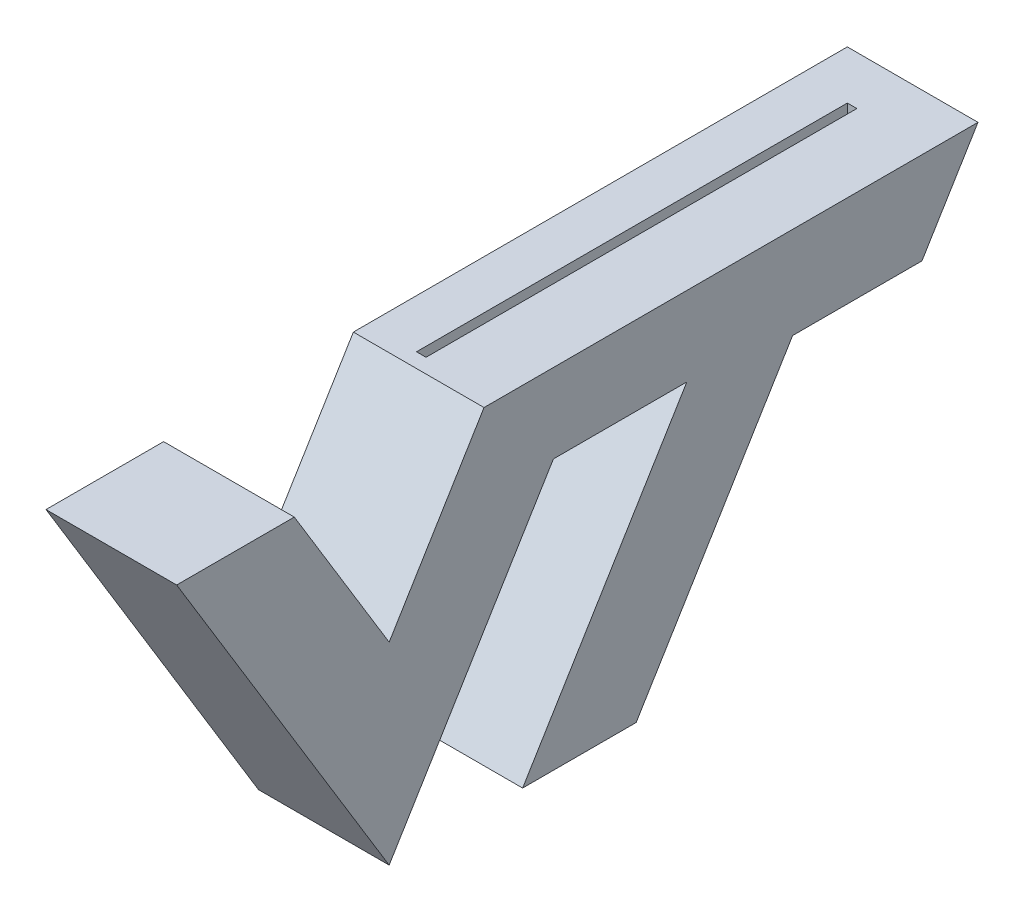
SolidWorks part; units mm, degrees
ref_plane "Front Plane" through (0, 0, 0) normal (0, 0, 1) x (1, 0, 0)
ref_plane "Top Plane" through (0, 0, 0) normal (0, 1, 0) x (1, 0, 0)
ref_plane "Right Plane" through (0, 0, 0) normal (1, 0, 0) x (0, 0, -1)
sketch "Sketch1" plane through (0, 0, 0) normal (1, 0, 0) x (0, 0, -1)
  line L0 (-48.1539, 15.6688) -> (-48.1539, -8.5378) construction
  line L1 (-80.0734, 20.9298) -> (-48.1539, -31.4755)
  line L2 (-16.2343, 20.9298) -> (-48.1539, -31.4755)
  line L3 (-80.0734, 20.9298) -> (-89.454, 36.3307)
  line L4 (-66.594, 36.3307) -> (-48.1539, 6.0559)
  line L5 (-29.7138, 36.3307) -> (-48.1539, 6.0559)
  line L6 (-16.2343, 20.9298) -> (9.7042, 20.9298)
  line L7 (9.7042, 20.9298) -> (-22.2153, -31.4755)
  line L8 (-22.2153, -31.4755) -> (-0.1479, -31.4755)
  line L9 (-0.1479, -31.4755) -> (30.2617, 18.4507)
  line L10 (30.2617, 18.4507) -> (55.4077, 18.4507)
  line L11 (55.4077, 18.4507) -> (66.2982, 36.3307)
  line L12 (66.2982, 36.3307) -> (-29.7138, 36.3307)
  line L13 (-66.594, 36.3307) -> (-89.454, 36.3307)
  line L14 (-73.6825, 21.4236) -> (-48.1539, -20.4892)
  line L15 (-20.955, 24.1657) -> (-48.1539, -20.4892)
  line L16 (-20.955, 24.1657) -> (17.5743, 24.1657)
  line L17 (17.5743, 24.1657) -> (-12.8352, -25.7605)
  line L18 (-12.8352, -25.7605) -> (-3.3586, -25.7605)
  line L19 (-3.3586, -25.7605) -> (27.051, 24.1657)
  line L20 (27.051, 24.1657) -> (52.197, 24.1657)
  line L21 (52.197, 24.1657) -> (56.1256, 30.6157)
  line L22 (56.1256, 30.6157) -> (-26.503, 30.6157)
  line L23 (-26.503, 30.6157) -> (-48.1539, -4.9304)
  line L24 (-69.8047, 30.6157) -> (-48.1539, -4.9304)
  line L25 (-69.8047, 30.6157) -> (-79.2813, 30.6157)
  line L26 (-73.6825, 21.4236) -> (-79.2813, 30.6157)
  point P1 (0, 0)
  point P2 (0, 0)
  point P4 (9.7042, 20.9298)
  dimension "D1" = 31.345
  dimension "D2" = 31.345
  dimension "D3" = 90
extrude "Boss-Extrude3" add sketch "Sketch1" along normal blind 25.4 contours L1 L2 L6 L7 L8 L9 L10 L11 L12 L5 L4 L13 L3
extrude "Cut-Extrude2" cut sketch "Sketch1<7>" along normal blind 20.32 from offset 2.54 contours L14 L15 L16 L17 L18 L19 L20 L21 L22 L23 L24 L25 L26
sketch "Sketch1<7>" plane through (0, 0, 0) normal (1, 0, 0) x (0, 0, -1) same geometry as "Sketch1"
sketch "Sketch4" plane through (0, 36.3307, 0) normal (0, 1, 0) x (1, 0, 0)
  line L1 (4.9967, 59.1862) -> (16.0423, 59.1862)
  line L2 (4.9967, 59.1862) -> (4.9967, -29.7138)
  line L3 (4.9967, -29.7138) -> (16.0423, -29.7138)
  line L4 (16.0423, 59.1862) -> (16.0423, -29.7138)
  line L5 (25.4, -29.7138) -> (0, -29.7138) construction
  line L6 (9.4419, 56.7338) -> (10.9623, 56.7338)
  line L7 (9.4419, 56.7338) -> (9.4419, -26.2393)
  line L8 (9.4419, -26.2393) -> (10.9623, -26.2393)
  line L9 (10.9623, 56.7338) -> (10.9623, -26.2393)
  dimension "D1" = 88.9
  dimension "D2" = 0
  dimension "D3" = 5.08
extrude "Boss-Extrude4" add sketch "Sketch4" against normal blind 11.684
sketch "Sketch6" plane through (0, 36.3307, 0) normal (0, 1, 0) x (1, 0, 0)
  line L1 (9.452, 56.8493) -> (11.3075, 56.8493)
  line L2 (9.452, 56.8493) -> (9.452, -26.8951)
  line L3 (9.452, -26.8951) -> (11.3075, -26.8951)
  line L4 (11.3075, 56.8493) -> (11.3075, -26.8951)
extrude "Cut-Extrude4" cut sketch "Sketch6" against normal blind 12.7
